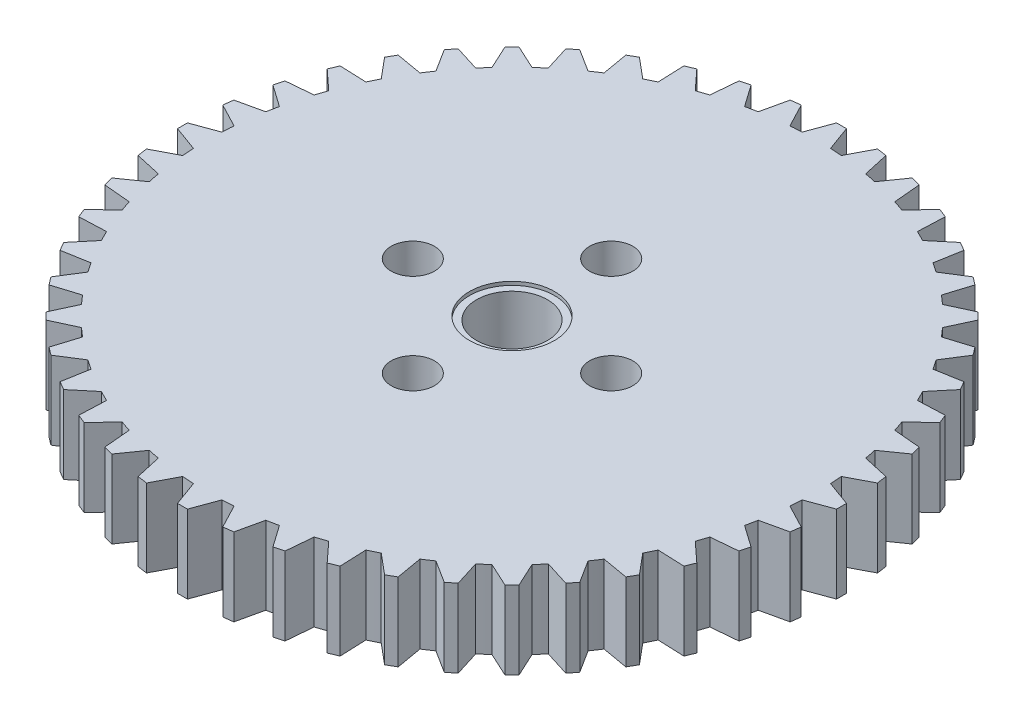
SolidWorks part; units mm, degrees
material "ABS"
ref_plane "Front" through (0, 0, 0) normal (0, 0, 1) x (1, 0, 0)
ref_plane "Top" through (0, 0, 0) normal (0, 1, 0) x (1, 0, 0)
ref_plane "Right" through (0, 0, 0) normal (1, 0, 0) x (0, 0, -1)
sketch "Sketch2" plane through (0, 0, 0) normal (0, 1, 0) x (1, 0, 0)
  circle A0 centre (0, 0) radius 21.5
  circle A1 centre (0, 0) radius 2.5
  dimension "D1" = 43
  dimension "D2" = 5
extrude "Boss-Extrude1" add sketch "Sketch2" along normal blind 5.5
ref_plane "Plane1" through (0, 3, 0) normal (0, 1, 0) x (1, 0, 0)
sketch "Sketch3" plane through (0, 3, 0) normal (0, 1, 0) x (1, 0, 0)
  line L0 (0, 21.5) -> (0, -21.5) construction
  line L1 (-21.5, 0) -> (21.5, 0) construction
  line L3 (0, 21.5) -> (0, 23.25) construction
  line L4 (-1, 21.4767) -> (-0.35, 23.25)
  line L5 (-0.35, 23.25) -> (0.35, 23.25)
  line L6 (1, 21.4767) -> (0.35, 23.25)
  circle A0 centre (0, 0) radius 21.5 construction
  arc A1 (-21.5, 0) -> (21.5, 0) centre (0, 0) ccw
  arc A2 (1, 21.4767) -> (-1, 21.4767) centre (0, 0) ccw
  dimension "D1" = 2
  dimension "D2" = 0.35
  dimension "D3" = 23.25
extrude "Boss-Extrude2" add sketch "Sketch3" along normal blind 2.5 and the other way blind 3 contours L6 L5 L4 A2
pattern_circular "CirPattern1" count 48 over 360 about axis through (0, 5.5, 0) along (0, 1, 0) of "Boss-Extrude2"
sketch "Sketch4" plane through (0, 5.5, 0) normal (0, 1, 0) x (1, 0, 0)
  circle A0 centre (0, 0) radius 3
  circle A1 centre (0, 0) radius 2.5
  circle A2 centre (0, 0) radius 2.5 construction
  dimension "D1" = 0.5
extrude "Cut-Extrude1" cut sketch "Sketch4" against normal blind 0.25
ref_plane "Plane2" through (0, 5.5, 0) normal (0, 1, 0) x (1, 0, 0)
sketch "Sketch5" plane through (0, 5.5, 0) normal (0, 1, 0) x (1, 0, 0)
  line L0 (-34.259, 0) -> (34.259, 0) construction
  line L1 (0, -34.259) -> (0, 34.259) construction
  circle A0 centre (0, 7) radius 1.525
  point P6 (0, 0)
  dimension "D1" = 7
  dimension "D2" = 3.05
extrude "Cut-Extrude2" cut sketch "Sketch5" against normal up to surface (5.5 mm away) up to face at (0, 0, 0)
pattern_circular "CirPattern2" count 4 over 360 about axis through (0, 5.25, 0) along (0, 1, 0) of "Cut-Extrude2"
